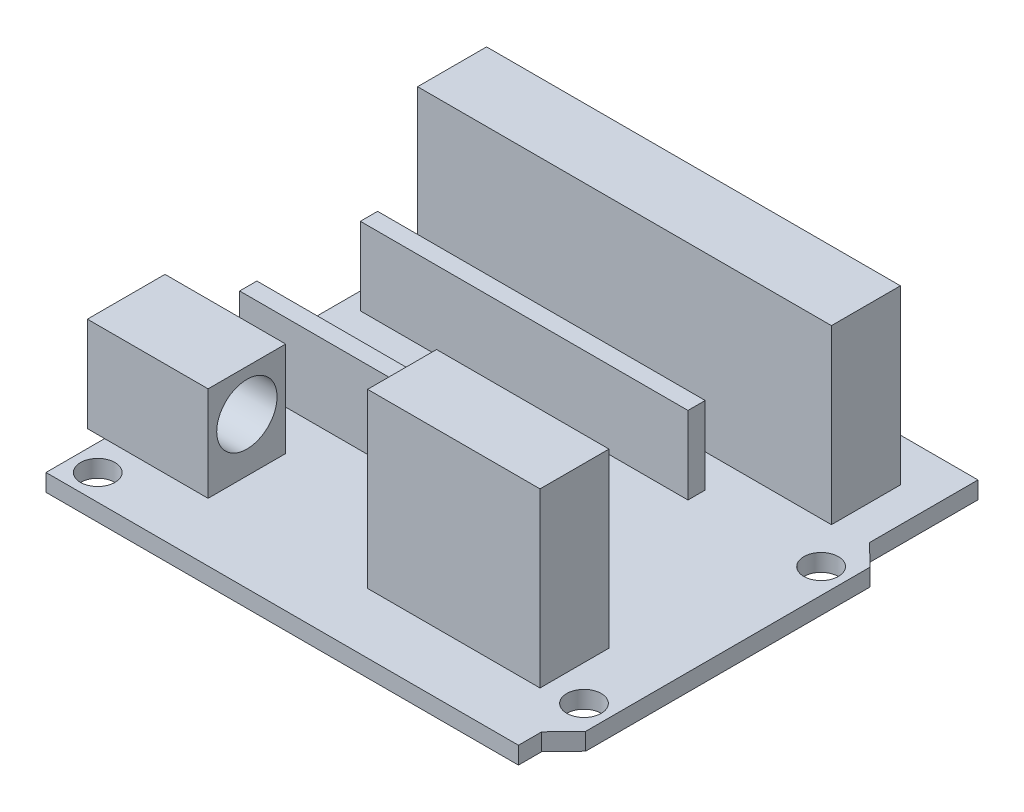
SolidWorks part; units mm, degrees
ref_plane "Front Plane" through (0, 0, 0) normal (0, 0, 1) x (1, 0, 0)
ref_plane "Top Plane" through (0, 0, 0) normal (0, 1, 0) x (1, 0, 0)
ref_plane "Right Plane" through (0, 0, 0) normal (1, 0, 0) x (0, 0, -1)
sketch "Sketch1" plane through (0, 0, 0) normal (0, 1, 0) x (1, 0, 0)
  line L0 (54.8, 53.3) -> (54.8, 40.7)
  line L1 (0, 0) -> (57.3, 0)
  line L2 (0, 0) -> (0, 53.3)
  line L3 (0, 53.3) -> (54.8, 53.3)
  line L4 (54.8, 40.7) -> (57.3, 38.3)
  line L5 (54.8, 0) -> (54.8, 2.6958)
  line L6 (0, 3) -> (3, 3) construction
  line L7 (3, 3) -> (3, 0) construction
  line L8 (54.8, 2.6958) -> (57.3, 5.3)
  line L9 (57.3, 5.3) -> (57.3, 0) construction
  line L10 (57.3, 38.3) -> (57.3, 5.3)
  line L11 (4, 53.3) -> (4, 50.8) construction
  line L12 (4, 50.8) -> (0, 50.8) construction
  line L13 (57.3, 8) -> (54.4, 8) construction
  line L14 (54.4, 8) -> (54.4, 10) construction
  line L15 (54.4, 8) -> (54.4, 0) construction
  line L16 (54.4, 35.5) -> (57.3, 35.5) construction
  line L17 (54.4, 35.5) -> (54.4, 53.3) construction
  circle A0 centre (3, 3) radius 2
  circle A1 centre (4, 50.8) radius 2
  circle A2 centre (54.4, 8) radius 2
  circle A3 centre (54.4, 35.5) radius 2
  point P19 (4, 50.8)
  point P20 (3, 3)
  point P30 (54.4, 35.5)
  point P31 (54.4, 8)
  dimension "D5" = 4
  dimension "D7" = 4
  dimension "D10" = 4
  dimension "D14" = 4
  dimension "D1" = 53.3
  dimension "D2" = 57.3
  dimension "D3" = 12.6
  dimension "D4" = 54.8
  dimension "D6" = 3
  dimension "D8" = 2.5
  dimension "D9" = 4
  dimension "D11" = 2.9
  dimension "D12" = 8
  dimension "D13" = 33
  dimension "D15" = 2.9
  dimension "D16" = 17.8
extrude "Boss-Extrude1" add sketch "Sketch1" along normal blind 2 contours L10 L4 L0 L3 L2 L1 L5 L8 A0 region at (28.2321, 0, -26.5425)
sketch "Sketch2" plane through (0, 2, 0) normal (0, 1, 0) x (1, 0, 0)
  line L0 (0, 34.4602) -> (2, 34.4602) construction
  line L1 (2, 36.4602) -> (40, 36.4602)
  line L2 (2, 36.4602) -> (2, 34.4602)
  line L3 (2, 34.4602) -> (40, 34.4602)
  line L4 (40, 36.4602) -> (40, 34.4602)
  line L5 (0, 0) -> (0, 53.3) construction
  dimension "D1" = 38
  dimension "D2" = 2
  dimension "D3" = 2
extrude "Boss-Extrude2" add sketch "Sketch2" along normal blind 9
pattern_linear "LPattern1" count 2 spacing 14 along (0, 0, 1) of "Boss-Extrude2"
sketch "Sketch3" plane through (0, 2, 0) normal (0, 1, 0) x (1, 0, 0)
  line L0 (57.3, 7) -> (50.3, 7) construction
  line L1 (57.3, 38.3) -> (57.3, 5.3) construction
  line L2 (50.3, 7) -> (50.3, 0) construction
  line L3 (0, 0) -> (54.8, 0) construction
  line L5 (50.3, 7) -> (30.3, 7)
  line L6 (50.3, 7) -> (50.3, 15)
  line L7 (50.3, 15) -> (30.3, 15)
  line L8 (30.3, 7) -> (30.3, 15)
  dimension "D1" = 7
  dimension "D2" = 7
  dimension "D3" = 20
  dimension "D4" = 8
extrude "Boss-Extrude3" add sketch "Sketch3" along normal blind 20
sketch "Sketch4" plane through (0, 2, 0) normal (0, 1, 0) x (1, 0, 0)
  line L0 (50.8, 53.3) -> (50.8, 48.3) construction
  line L1 (0, 53.3) -> (54.8, 53.3) construction
  line L2 (50.8, 48.3) -> (54.8, 48.3) construction
  line L3 (54.8, 53.3) -> (54.8, 40.7) construction
  line L5 (50.8, 48.3) -> (2.8, 48.3)
  line L6 (50.8, 48.3) -> (50.8, 40.3)
  line L7 (50.8, 40.3) -> (2.8, 40.3)
  line L8 (2.8, 48.3) -> (2.8, 40.3)
  dimension "D1" = 5
  dimension "D2" = 4
  dimension "D3" = 48
  dimension "D4" = 8
extrude "Boss-Extrude4" add sketch "Sketch4" along normal blind 20
ref_plane "Plane1" through (-2, 0, 0) normal (-1, 0, 0) x (0, 0, 1)
sketch "Sketch5" plane through (-2, 0, 0) normal (-1, 0, 0) x (0, 0, 1)
  line L0 (0, 2) -> (-53.3, 2) construction
  line L1 (-6.8, 2) -> (-15.8, 2)
  line L2 (-6.8, 2) -> (-6.8, 13)
  line L3 (-6.8, 13) -> (-15.8, 13)
  line L4 (-15.8, 2) -> (-15.8, 13)
  line L5 (0, 2) -> (-6.8, 2) construction
  line L6 (-11.3, 13) -> (-11.3, 8.2) construction
  circle A0 centre (-11.3, 8.2) radius 3.5
  dimension "D5" = 7
  dimension "D1" = 6.8
  dimension "D2" = 9
  dimension "D3" = 11
  dimension "D4" = 4.8
extrude "Boss-Extrude5" add sketch "Sketch5" against normal blind 14
sketch "Sketch6" plane through (0, 0, 0) normal (0, -1, 0) x (1, 0, 0)
  circle A0 centre (6.4883, -7.768) radius 0.5
  dimension "D1" = 1
extrude "Boss-Extrude6" add sketch "Sketch6" along normal blind 2.2
sketch "Sketch7" plane through (0, 0, 0) normal (0, -1, 0) x (1, 0, 0)
  line L0 (6.4883, -7.768) -> (11.8863, -9.8733)
pattern_linear "LPattern2" count 2 spacing 5 along (0.9317, 0, -0.3634) of "Boss-Extrude6"
pattern_linear "LPattern3" count 2 spacing 5 along (0, 0, -1) of "Boss-Extrude6"
